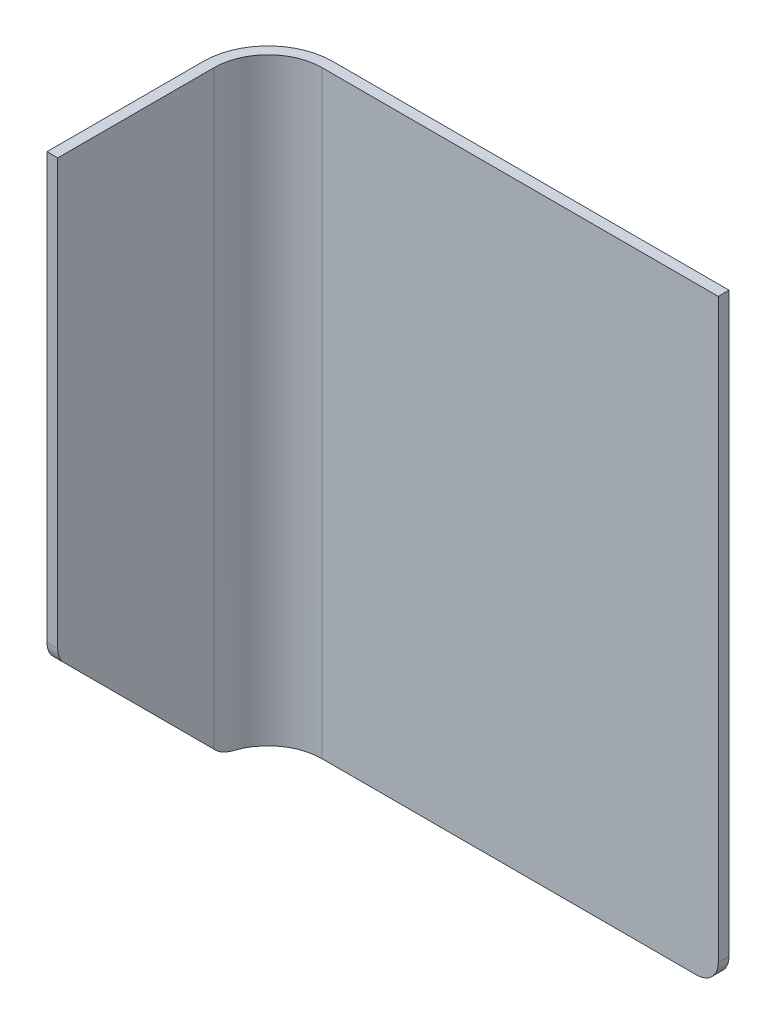
SolidWorks part; units mm, degrees
ref_plane "Спереди" through (0, 0, 0) normal (0, 0, 1) x (1, 0, 0)
ref_plane "Сверху" through (0, 0, 0) normal (0, 1, 0) x (1, 0, 0)
ref_plane "Справа" through (0, 0, 0) normal (1, 0, 0) x (0, 0, -1)
sketch "Эскиз1" plane through (0, 0, 0) normal (0, 1, 0) x (1, 0, 0)
  line L0 (43.8752, 20.9261) -> (-29.6248, 20.9261)
  line L1 (-41.6248, 8.9261) -> (-41.6248, -20.0739)
  line L2 (-39.6248, -20.0739) -> (-39.6248, 8.9261)
  line L3 (-29.6248, 18.9261) -> (43.8752, 18.9261)
  line L4 (-41.6248, -20.0739) -> (-39.6248, -20.0739)
  line L5 (43.8752, 20.9261) -> (43.8752, 18.9261)
  arc A1 (-39.6248, 8.9261) -> (-29.6248, 18.9261) centre (-29.6248, 8.9261) cw
  arc A2 (-41.6248, 8.9261) -> (-29.6248, 20.9261) centre (-29.6248, 8.9261) cw
  dimension "D2" = 10
  dimension "D3" = 12
  dimension "D1" = 2
  dimension "D4" = 2
  dimension "D5" = 39
  dimension "D6" = 85.5
extrude "Бобышка-Вытянуть1" add sketch "Эскиз1" against normal blind 111
sketch "Эскиз2" plane through (-41.6248, 0, 0) normal (-1, 0, 0) x (0, 0, 1)
  line L0 (-20.9261, -111) -> (-10.4361, -111)
  line L2 (-20.9261, -111) -> (-8.9261, -111) construction
  line L3 (20.0739, 0) -> (20.0739, -80.49)
  line L4 (20.0739, -111) -> (20.0739, 0) construction
  line L5 (20.0739, -80.49) -> (-10.4361, -111)
  line L6 (-20.9261, -111) -> (-20.9261, 0) construction
  dimension "D1" = 10.49
  dimension "D2" = 80.49
  dimension "D3" = 43.1477
  dimension "D5" = 41
extrude "Вырез-Вытянуть1" cut sketch "Эскиз2" against normal through all and the other way through all
sketch "Эскиз3" plane through (-41.6248, 0, 0) normal (-1, 0, 0) x (0, 0, 1)
  line L0 (-7.3732, -107.9371) -> (-31.4165, -83.8971)
  line L1 (-8.9261, -109.49) -> (20.0739, -80.49) construction
  line L2 (-20.9261, -111) -> (-10.4361, -111) construction
  line L3 (-31.4165, -83.8971) -> (-7.0796, -59.5569)
  line L4 (-20.9261, -111) -> (-20.9261, 0) construction
  line L5 (-7.0796, -59.5569) -> (16.9637, -83.6002)
  line L6 (16.9637, -83.6002) -> (-7.3732, -107.9371)
  dimension "D1" = 90
  dimension "D2" = 34
  dimension "D5" = 51.4431
  dimension "D6" = 13.8465
fillet "Скругление1" radius 4 3 edges at (-40.5197, -111, -10.4361) (-40.6248, -80.49, 20.0739) (43.8752, -111, -19.9261)
